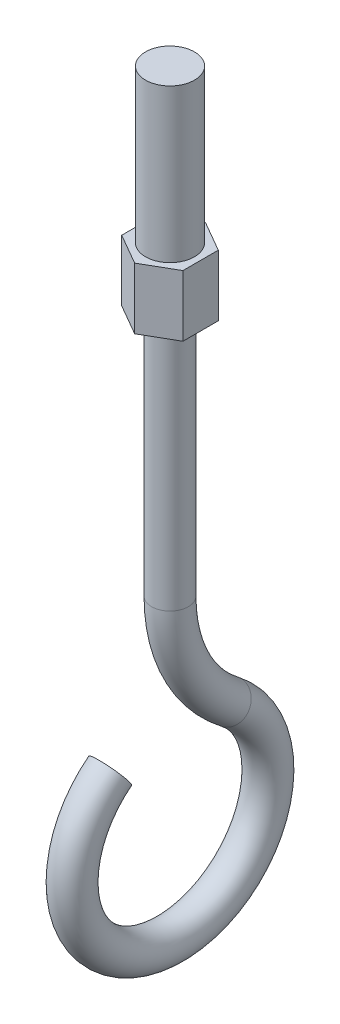
SolidWorks part; units mm, degrees
material "Alloy Steel"
ref_plane "Front Plane" through (0, 0, 0) normal (0, 0, 1) x (1, 0, 0)
ref_plane "Top Plane" through (0, 0, 0) normal (0, 1, 0) x (1, 0, 0)
ref_plane "Right Plane" through (0, 0, 0) normal (1, 0, 0) x (0, 0, -1)
sketch "Sketch1" plane through (0, 0, 0) normal (1, 0, 0) x (0, 0, -1)
  line L0 (0, 0) -> (0, -50.8)
  arc A0 (0, -50.8) -> (12.3902, -75.9647) centre (31.75, -50.8) ccw
  arc A1 (12.3902, -75.9647) -> (-12.3902, -75.9647) centre (0, -92.0701) cw
  dimension "D2" = 31.75
  dimension "D3" = 20.32
  dimension "D1" = 50.8
sweep "Sweep1" add path "Sketch1" circular profile diameter 7.62 parameters "D3"=7.62
sketch "Sketch32" plane through (0, 0, 0) normal (0, 1, 0) x (1, 0, 0)
  line L1 (6.35, 3.6662) -> (0, 7.3323)
  line L2 (0, 7.3323) -> (-6.35, 3.6662)
  line L3 (-6.35, 3.6662) -> (-6.35, -3.6662)
  line L4 (-6.35, -3.6662) -> (0, -7.3323)
  line L5 (0, -7.3323) -> (6.35, -3.6662)
  line L6 (6.35, -3.6662) -> (6.35, 3.6662)
  circle A0 centre (0, 0) radius 6.35 construction
  circle A1 centre (0, 0) radius 5.08
  circle M8 centre (0, 0) radius 3.81
  dimension "D1" = 10.16
  dimension "D2" = 12.7
extrude "Boss-Extrude1" add sketch "Sketch32" along normal blind 12.7 separate body
extrude "Boss-Extrude2" add sketch "Sketch32<2>" along normal offset from surface (44.45 mm away) 31.75 contours M8 | A1 M8 region at (-4.9363, 0, 0) region at (0, 0, 0) up to face at (0, 12.7, 0) offset beyond the face yes
sketch "Sketch32<2>" plane through (0, 0, 0) normal (0, 1, 0) x (1, 0, 0) same geometry as "Sketch32"
